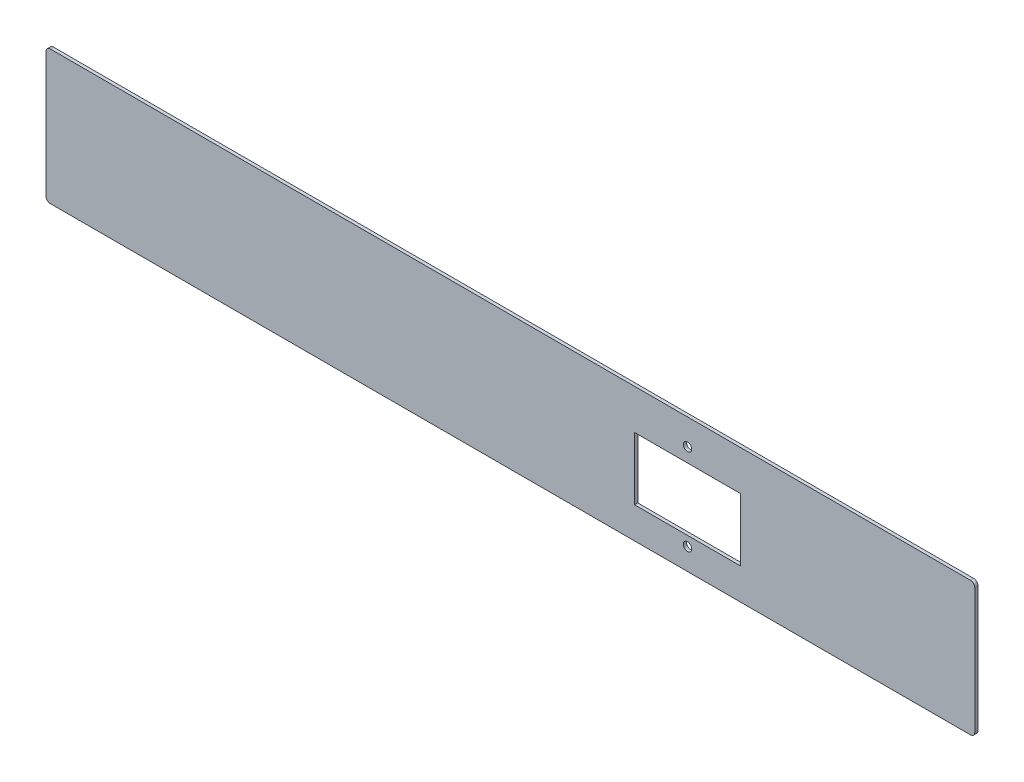
SolidWorks part; units mm, degrees
ref_plane "Front Plane" through (0, 0, 0) normal (0, 0, 1) x (1, 0, 0)
ref_plane "Top Plane" through (0, 0, 0) normal (0, 1, 0) x (1, 0, 0)
ref_plane "Right Plane" through (0, 0, 0) normal (1, 0, 0) x (0, 0, -1)
sketch "Sketch1" plane through (0, 0, 0) normal (0, 0, 1) x (1, 0, 0)
  line L1 (-351.9248, 29.7035) -> (78.0752, 29.7035)
  line L2 (-351.9248, 29.7035) -> (-351.9248, -32.2965)
  line L3 (-351.9248, -32.2965) -> (78.0752, -32.2965)
  line L4 (78.0752, 29.7035) -> (78.0752, -32.2965)
  line L5 (-79.4248, 11.2035) -> (-30.4248, 11.2035)
  line L6 (-79.4248, 11.2035) -> (-79.4248, -17.7965)
  line L7 (-79.4248, -17.7965) -> (-30.4248, -17.7965)
  line L8 (-30.4248, 11.2035) -> (-30.4248, -17.7965)
  circle A0 centre (-54.9248, 17.7035) radius 1.95
  circle A1 centre (-54.9248, -22.2965) radius 1.95
  point P12 (-54.9248, 11.2035)
  dimension "D3" = 133
  dimension "D4" = 40
  dimension "D1" = 430
  dimension "D2" = 62
  dimension "D5" = 10
  dimension "D6" = 49
  dimension "D7" = 29
  dimension "D8" = 6.5
extrude "Boss-Extrude1" add sketch "Sketch1" along normal blind 1.5
fillet "Fillet1" radius 2 4 edges at (78.0752, 29.7035, 0.75) (78.0752, -32.2965, 0.75) (-351.9248, -32.2965, 0.75) (-351.9248, 29.7035, 0.75)
